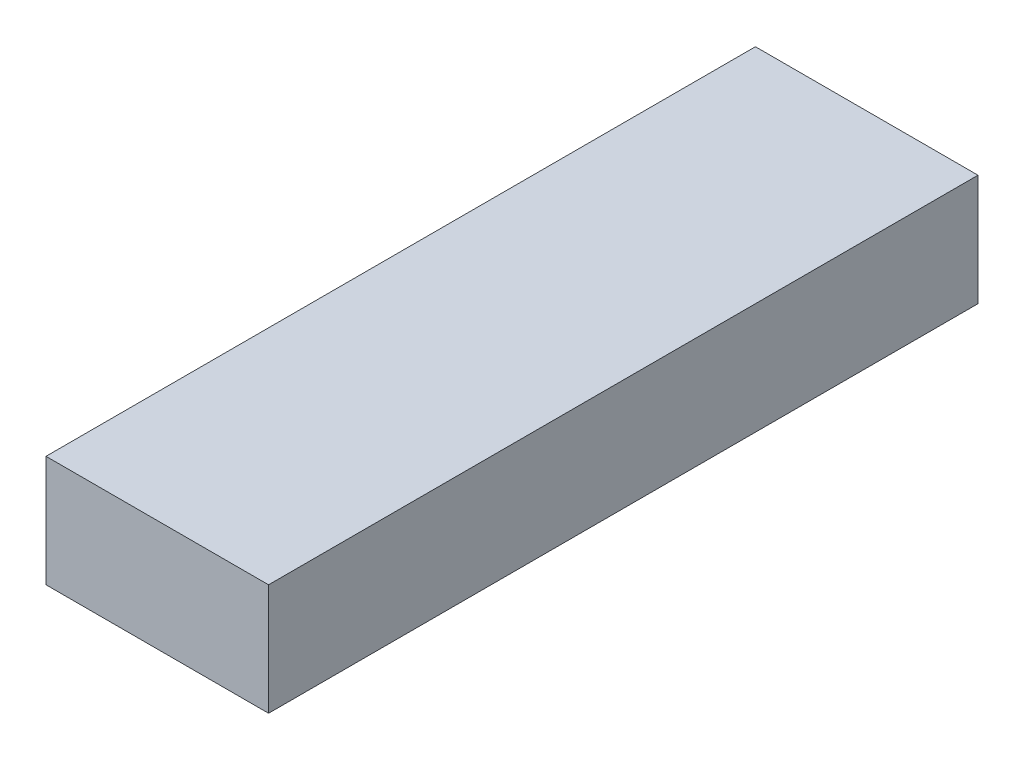
SolidWorks part; units mm, degrees
ref_plane "Front Plane" through (0, 0, 0) normal (0, 0, 1) x (1, 0, 0)
ref_plane "Top Plane" through (0, 0, 0) normal (0, 1, 0) x (1, 0, 0)
ref_plane "Right Plane" through (0, 0, 0) normal (1, 0, 0) x (0, 0, -1)
sketch "Sketch1" plane through (0, 0, 0) normal (0, 0, 1) x (1, 0, 0)
  line L1 (-16, -8) -> (16, -8)
  line L2 (-16, -8) -> (-16, 8)
  line L3 (-16, 8) -> (16, 8)
  line L4 (16, -8) -> (16, 8)
  line L5 (-16, -8) -> (16, 8) construction
  line L6 (-16, 8) -> (16, -8) construction
  point P0 (0, 0)
  dimension "D1" = 16
  dimension "D2" = 31.9999
extrude "Boss-Extrude1" add sketch "Sketch1" along normal mid plane 101.9998
equation "\"D2@Sketch1\"=\"Batt X@Quad Assemb.sldasm\""
equation "\"D1@Sketch1\"=\"Batt Z@Quad Assemb.sldasm\""
equation "\"D1@Boss-Extrude1\"=\"Batt Y@Quad Assemb.sldasm\""
